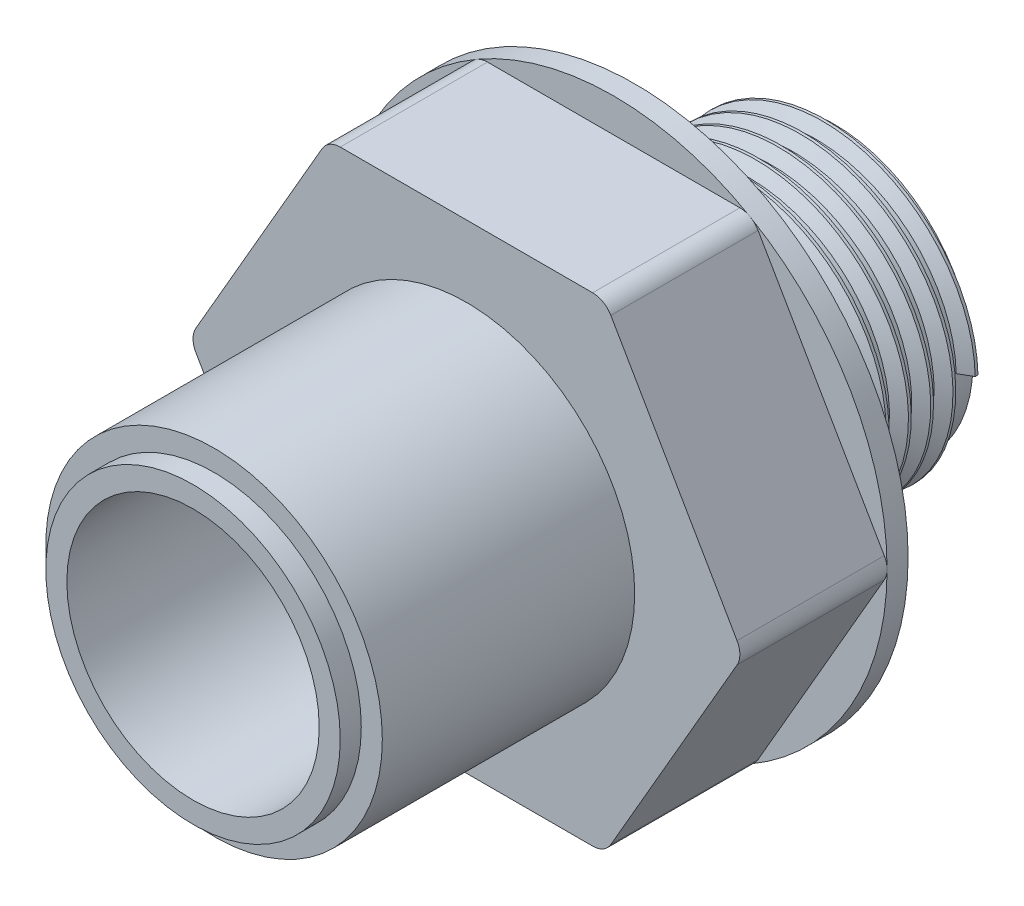
SolidWorks part; units mm, degrees
ref_plane "Front Plane" through (0, 0, 0) normal (0, 0, 1) x (1, 0, 0)
ref_plane "Top Plane" through (0, 0, 0) normal (0, 1, 0) x (1, 0, 0)
ref_plane "Right Plane" through (0, 0, 0) normal (1, 0, 0) x (0, 0, -1)
sketch "Sketch2" plane through (0, 0, 0) normal (1, 0, 0) x (0, 0, -1)
  line L0 (-17.6659, 0) -> (22.2536, 0) construction
  line L1 (0, 4.25) -> (30.5, 4.25)
  line L2 (30.5, 4.25) -> (30.5, 6.58)
  line L3 (30.5, 6.58) -> (21, 6.58)
  line L4 (21, 6.58) -> (21, 13)
  line L5 (21, 13) -> (13, 13)
  line L8 (13, 13) -> (13, 8)
  line L9 (13, 8) -> (0, 8)
  line L10 (0, 8) -> (0, 4.25)
  dimension "D1" = 30.5
  dimension "D2" = 21
  dimension "D3" = 8
  dimension "D4" = 13
  dimension "D5" = 4.25
  dimension "D8" = 6.58
  dimension "D9" = 8
revolve "Revolve1" add sketch "Sketch2" angle 360 about L0
thread "Thread1" pitch 1.0583 method extrude profile "Thread Profile1" start angle 0, offset 0, length 0, pitch 1.0583, diameter 13.16
ref_plane "Plane1" through (6.58, 0, -30.5) normal (0, -1, 0) x (1, 0, 0)
sketch "Thread Profile1" plane through (6.58, 0, -30.5) normal (0, -1, 0) x (1, 0, 0)
  line L0 (0, 0) -> (0, 1.0583) construction
  line L1 (0, 0) -> (0.5728, 0.3307)
  line L2 (0.5728, 0.3307) -> (0.5728, 0.463)
  line L3 (0.5728, 0.463) -> (0, 0.7937)
  line L4 (0.5728, 0.3969) -> (0, 0.3969) construction
  line L11 (0, 0) -> (0, 0.7937)
  point P2 (0, 0)
  dimension "Pitch" = 1.0583
  dimension "Profile_Angle" = 60
  dimension "Profile_Land" = 0.1323
  dimension "Profile_Height" = 0.5728
sketch "Sketch6" plane through (0, 0, 0) normal (0, 0, 1) x (1, 0, 0)
  circle A0 centre (0, 0) radius 7
  circle A1 centre (0, 0) radius 8 construction
  dimension "D1" = 1
extrude "Cut-Extrude1" cut sketch "Sketch6" against normal blind 1 flip side to cut
sketch "Sketch8" plane through (0, 0, -13) normal (0, 0, 1) x (1, 0, 0)
  line L0 (-6, 11.3923) -> (6, 11.3923)
  line L1 (6.866, 10.8923) -> (12.866, 0.5)
  line L2 (12.866, -0.5) -> (6.866, -10.8923)
  line L3 (6, -11.3923) -> (-6, -11.3923)
  line L4 (-6.866, -10.8923) -> (-12.866, -0.5)
  line L5 (-12.866, 0.5) -> (-6.866, 10.8923)
  arc A0 (6, 11.3923) -> (6.866, 10.8923) centre (6, 10.3923) cw
  arc A1 (12.866, 0.5) -> (12.866, -0.5) centre (12, 0) cw
  arc A2 (6.866, -10.8923) -> (6, -11.3923) centre (6, -10.3923) cw
  arc A3 (-6, -11.3923) -> (-6.866, -10.8923) centre (-6, -10.3923) cw
  arc A4 (-12.866, -0.5) -> (-12.866, 0.5) centre (-12, 0) cw
  arc A5 (-6, 11.3923) -> (-6.866, 10.8923) centre (-6, 10.3923) ccw
  circle A6 centre (0, 0) radius 13 construction
  dimension "D1" = 1
extrude "Cut-Extrude3" cut sketch "Sketch8" against normal blind 7 flip side to cut
sketch "Sketch9" plane through (0, 0, 0) normal (0, 0, 1) x (1, 0, 0)
  circle A0 centre (0, 0) radius 6
extrude "Cut-Extrude4" cut sketch "Sketch9" against normal up to surface (21 mm away) up to face at (13, 0, -21)
